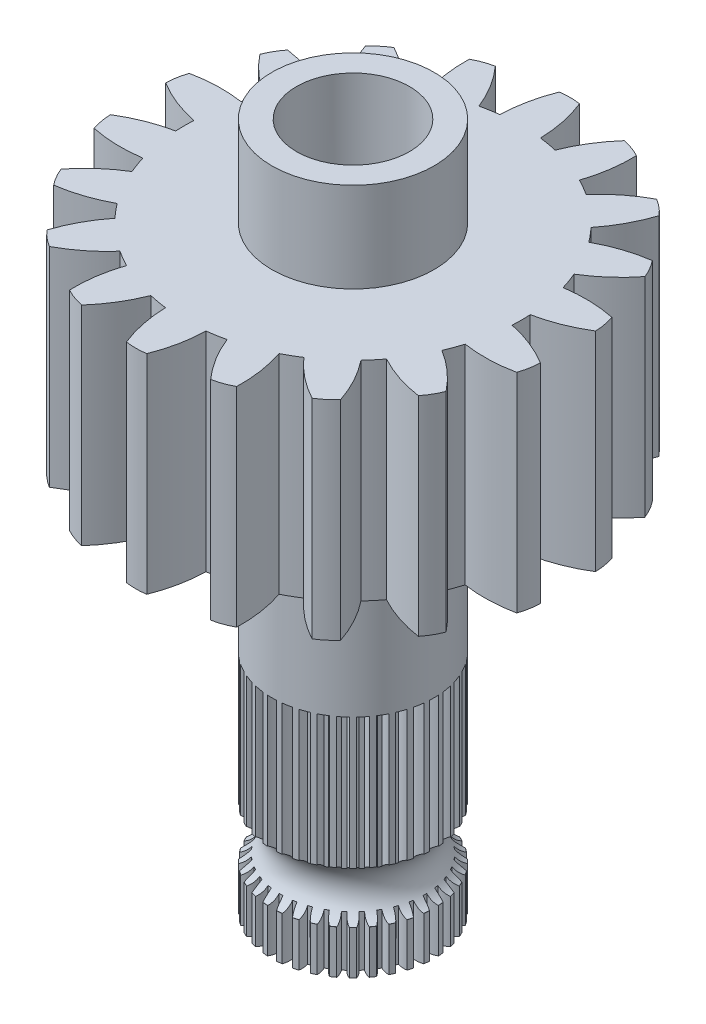
SolidWorks part; units mm, degrees
material "AISI 4130 Steel, annealed at 865C"
ref_plane "Front Plane" through (0, 0, 0) normal (0, 0, 1) x (1, 0, 0)
ref_plane "Top Plane" through (0, 0, 0) normal (0, 1, 0) x (1, 0, 0)
ref_plane "Right Plane" through (0, 0, 0) normal (1, 0, 0) x (0, 0, -1)
sketch "Sketch1" plane through (0, 0, 0) normal (0, 1, 0) x (1, 0, 0)
  circle A0 centre (0, 0) radius 21.15
  dimension "D1" = 42.3
extrude "Boss-Extrude1" add sketch "Sketch1" along normal blind 20.3
sketch "Sketch2" plane through (0, 20.3, 0) normal (0, 1, 0) x (1, 0, 0)
  circle A0 centre (0, 0) radius 7.9
  dimension "D1" = 15.8
extrude "Boss-Extrude2" add sketch "Sketch2" along normal blind 8.75
sketch "Sketch3" plane through (0, 0, 0) normal (0, -1, 0) x (1, 0, 0)
  circle A0 centre (0, 0) radius 7.9
  dimension "D1" = 15.8
extrude "Boss-Extrude3" add sketch "Sketch3" along normal blind 37.8
sketch "Sketch4" plane through (0, 0, 0) normal (0, -1, 0) x (1, 0, 0)
  line L3 (0, 21.15) -> (0, 16.4) construction
  arc A0 (1.9732, 16.2809) -> (-1.9732, 16.2809) centre (0, 0) ccw
  arc A3 (0.9888, 21.0727) -> (-0.9888, 21.0727) centre (0, 14.7904) ccw
  arc A4 (-0.9888, 21.0727) -> (-1.9732, 16.2809) centre (11.9241, 15.9228) ccw
  arc A5 (0.9888, 21.0727) -> (1.9732, 16.2809) centre (-11.9241, 15.9228) cw
  point P6 (0, 21.15)
sketch "Sketch5" plane through (0, 0, 0) normal (0, -1, 0) x (1, 0, 0)
  circle A0 centre (0, 0) radius 16.4
  circle A1 centre (0, 0) radius 21.15
extrude "Cut-Extrude2" cut sketch "Sketch5" against normal blind 27 contours A1 | A0
extrude "Boss-Extrude4" add sketch "Sketch4" against normal blind 20.3
pattern_circular "CirPattern1" count 18 over 360 about axis through (0, 0, 0) along (0, -1, 0) of "Boss-Extrude4"
sketch "Sketch6" plane through (0, 29.05, 0) normal (0, 1, 0) x (1, 0, 0)
  circle A0 centre (0, 0) radius 3.5
extrude "Cut-Extrude3" cut sketch "Sketch6" against normal blind 5
sketch "Sketch7" plane through (0, -37.8, 0) normal (0, -1, 0) x (1, 0, 0)
  line L0 (0, 7) -> (0, 7.9) construction
  arc A0 (0.4371, 7.8879) -> (-0.4371, 7.8879) centre (0, 0) ccw
  arc A1 (0.185, 6.9976) -> (-0.185, 6.9976) centre (0, 0) ccw
  arc A2 (0.4371, 7.8879) -> (0.185, 6.9976) centre (2.0908, 6.9389) ccw
  arc A3 (-0.4371, 7.8879) -> (-0.185, 6.9976) centre (-2.0908, 6.9389) cw
extrude "Cut-Extrude4" cut sketch "Sketch7" against normal blind 22
pattern_circular "CirPattern2" count 36 over 360 about axis through (0, -37.8, 0) along (0, -1, 0) of "Cut-Extrude4"
sketch "Sketch8" plane through (0, 0, 0) normal (0, 0, 1) x (1, 0, 0)
  line L1 (7.8879, -33.55) -> (7.844, -37.8) construction
  line L2 (7.844, -15.8) -> (7.844, -37.8) construction
  line L3 (7.8879, -15.8) -> (7.8879, -37.8) construction
  line L5 (7.8879, -33.55) -> (8.6413, -33.55)
  line L6 (8.6413, -33.55) -> (8.6413, -28.5503)
  line L7 (8.6413, -28.5503) -> (7.844, -28.5503)
  arc A1 (7.844, -28.5503) -> (7.8879, -33.55) centre (9.1535, -31.0388) ccw
  dimension "D1" = 4.9997
  dimension "D2" = 0.7534
  dimension "D3" = 4.25
ref_axis "Pinion Axis" through (0, -41.1425, 0) along (0, 1, 0)
revolve "Cut-Revolve1" cut sketch "Sketch8" angle 360 about axis through (0, -41.1425, 0) along (0, 1, 0)
sketch "Sketch9" plane through (0, 29.05, 0) normal (0, 1, 0) x (1, 0, 0)
  circle A0 centre (0, 0) radius 5.5
extrude "Cut-Extrude5" cut sketch "Sketch9" against normal blind 14.5
sketch "Sketch10" plane through (0, 14.55, 0) normal (0, 1, 0) x (1, 0, 0)
  line L0 (0, 5.5) -> (0, -5.5) construction
  line L1 (-1.5, 5.2915) -> (-1.5, -5.2915)
  line L2 (1.5, 5.2915) -> (1.5, -5.2915)
  line L3 (1.5, 5.5) -> (1.5, -5.5) construction
  line L4 (-1.5, 5.5) -> (-1.5, -5.5) construction
  circle A0 centre (0, 0) radius 5.5 construction
  circle A3 centre (0, 0) radius 5.5
  circle A4 centre (0, 0) radius 5.5
  circle M4 centre (0, 0) radius 5.5
  dimension "D1" = 0
  dimension "D2" = 1.5
  dimension "D3" = 1.5
extrude "Boss-Extrude5" add sketch "Sketch10" along normal blind 3.5 contours L1 M4 | L2 M4 region at (-3.1635, 14.55, 0) region at (3.1635, 14.55, 0)
sketch "Sketch11" plane through (0, -37.8, 0) normal (0, -1, 0) x (1, 0, 0)
  circle A0 centre (0, 0) radius 5.5
extrude "Cut-Extrude6" cut sketch "Sketch11" against normal blind 51
